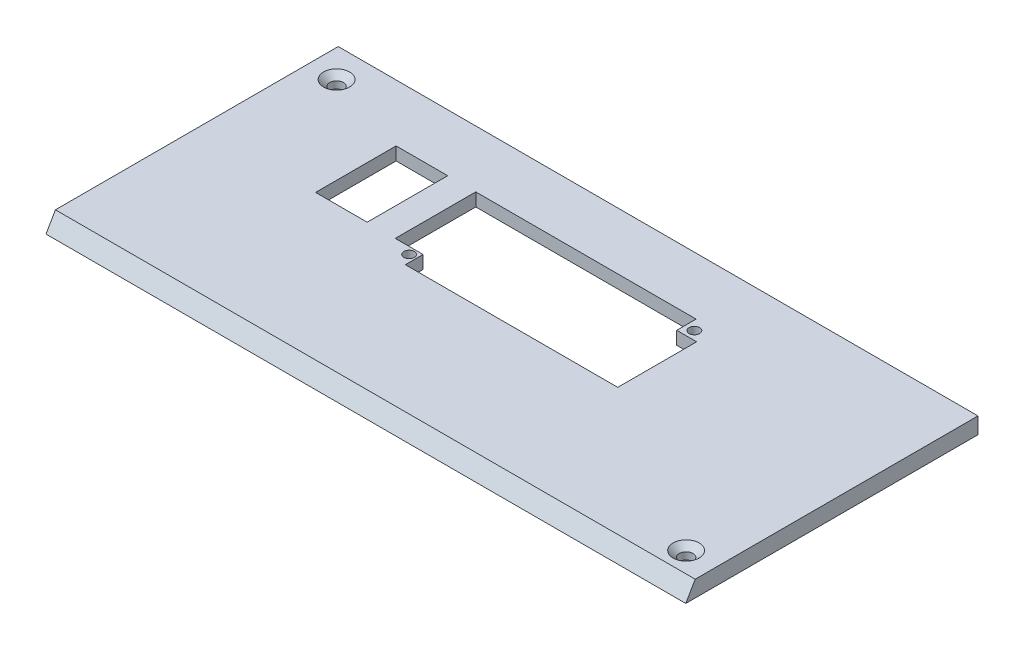
SolidWorks part; units mm, degrees
ref_plane "Alzado" through (0, 0, 0) normal (0, 0, 1) x (1, 0, 0)
ref_plane "Planta" through (0, 0, 0) normal (0, 1, 0) x (1, 0, 0)
ref_plane "Vista lateral" through (0, 0, 0) normal (1, 0, 0) x (0, 0, -1)
sketch "Croquis1" plane through (0, 0, 0) normal (1, 0, 0) x (0, 0, -1)
  line L0 (0, 0) -> (89.52, 0)
  line L1 (89.52, 0) -> (89.52, 5)
  line L2 (89.52, 5) -> (2.8868, 5)
  line L3 (0, 0) -> (2.8868, 5)
  dimension "D1" = 89.52
  dimension "D2" = 5
  dimension "D3" = 120
extrude "Saliente-Extruir1" add sketch "Croquis1" along normal blind 196
shell "Vaciado1" thickness 4 removed face at (98, 0, -44.76)
sketch "Sketch1" plane through (0, 1, 0) normal (0, -1, 0) x (-1, 0, 0)
  line L0 (0, 89.52) -> (-196, 89.52) construction
  line L1 (-98, 89.52) -> (-98, -14.2345)
sketch "Sketch2" plane through (0, 1, 0) normal (0, -1, 0) x (-1, 0, 0)
  line L0 (-59.6372, 47.3551) -> (-68.1615, 47.3551)
  line L5 (-68.1615, 47.3551) -> (-68.1615, 41.923)
  line L6 (-68.1615, 41.923) -> (-133.2369, 41.923)
  line L7 (-133.2369, 41.923) -> (-133.2369, 66.0933)
  line L8 (-133.2369, 66.0933) -> (-127.1352, 66.0933)
  line L9 (-127.1352, 66.0933) -> (-127.1352, 72.023)
  line L10 (-127.1352, 72.023) -> (-59.6372, 72.023)
  line L11 (-59.6372, 72.023) -> (-59.6372, 47.3551)
  circle A0 centre (-66.0169, 45.223) radius 1.6
  circle A1 centre (-129.9169, 68.723) radius 1.6
  point P4 (-97.9669, 56.973)
extrude "Cut-Extrude1" cut sketch "Sketch2" against normal blind 4.9
sketch "Sketch3" plane through (0, 5, 0) normal (0, 1, 0) x (1, 0, 0)
  line L0 (59.6372, 72.023) -> (42.4477, 72.023) construction
  line L1 (42.4477, 72.023) -> (42.4477, 47.3551) construction
  line L2 (42.4477, 47.3551) -> (59.6372, 47.3551) construction
  line L4 (51.0425, 47.3551) -> (35.2343, 47.3551)
  line L5 (51.0425, 47.3551) -> (51.0425, 72.023)
  line L6 (51.0425, 72.023) -> (35.2343, 72.023)
  line L7 (35.2343, 47.3551) -> (35.2343, 72.023)
  line L8 (51.0425, 47.3551) -> (35.2343, 72.023) construction
  line L9 (51.0425, 72.023) -> (35.2343, 47.3551) construction
  point P8 (43.1384, 59.6891)
extrude "Cut-Extrude2" cut sketch "Sketch3" against normal blind 10
sketch "Sketch4" plane through (0, 1, 0) normal (0, -1, 0) x (-1, 0, 0)
  circle A0 centre (-8.5, 80.52) radius 1.585
  circle A1 centre (-187, 9.1109) radius 1.585
extrude "Cut-Extrude3" cut sketch "Sketch4" against normal blind 13
hole_wizard "Avellanado para tornillo con cabeza avellanada en cruz de M3.51" positions "3DSketch1" profile "Sketch5" countersink size "M3.5" standard "AS"
sketch3d "3DSketch1"
  line L0 (187, 5, -9.1109) -> (187, 1, -9.1109) construction
  line L1 (8.5, 5, -80.52) -> (8.5, 1, -80.52) construction
  point P0 (187, 5, -9.1109)
  point P4 (8.5, 5, -80.52)
sketch "Sketch5" plane through (187, 5, -9.1109) normal (1, 0, 0) x (0, 0, 1)
  line L0 (0, 0) -> (0, 11.2618)
  line L1 (0, 11.2618) -> (2.1, 10)
  line L2 (2.1, 10) -> (2.1, 1.8348)
  line L3 (2.1, 1.8348) -> (4, 0)
  line L5 (4, 0) -> (0, 0)
  line L6 (-2.1, 1.8348) -> (-4, 0) construction
  line L10 (0, 11.2618) -> (-2.1, 10) construction
  line L11 (0, -6.35) -> (0, 107.95) construction
  dimension "Diámetro de taladro" = 4.2
  dimension "Profundidad de taladro" = 10
  dimension "Ángulo de avellanado cercano" = 8
  dimension "Ángulo de avellanado lejano" = 92
  dimension "Ángulo de perforador" = 118
